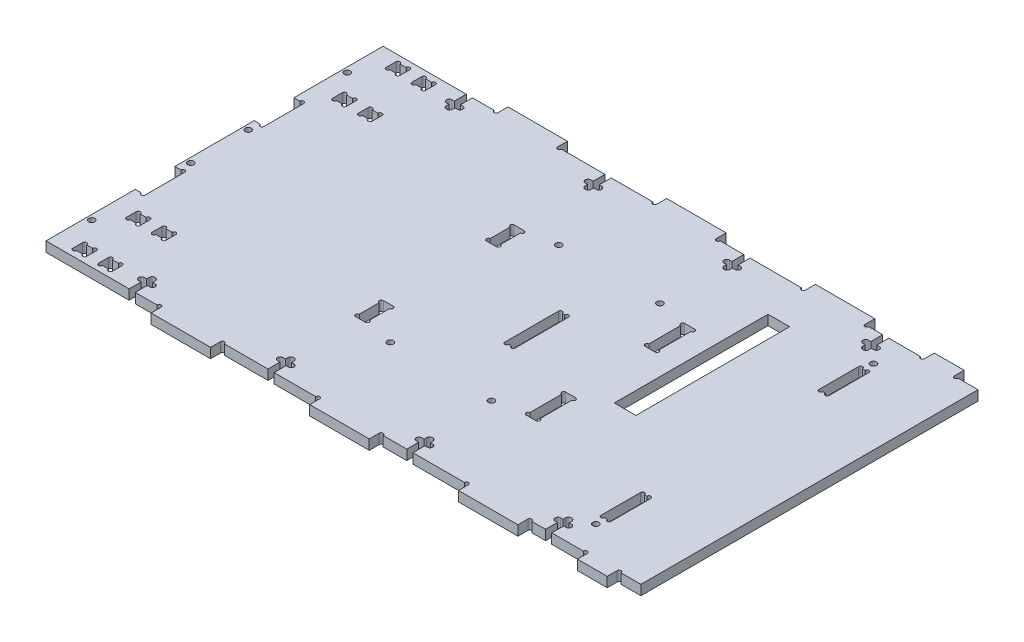
SolidWorks part; units mm, degrees
ref_plane "정면" through (0, 0, 0) normal (0, 0, 1) x (1, 0, 0)
ref_plane "윗면" through (0, 0, 0) normal (0, 1, 0) x (1, 0, 0)
ref_plane "우측면" through (0, 0, 0) normal (1, 0, 0) x (0, 0, -1)
sketch "스케치1" plane through (0, 0, 0) normal (0, 1, 0) x (1, 0, 0)
  line L1 (0, 0) -> (300, 0)
  line L2 (0, 0) -> (0, 170)
  line L3 (0, 170) -> (300, 170)
  line L4 (300, 0) -> (300, 170)
  dimension "D1" = 170
  dimension "D2" = 300
extrude "보스-돌출1" add sketch "스케치1" along normal blind 5
sketch "스케치2" plane through (0, 0, 0) normal (0, -1, 0) x (1, 0, 0)
  line L0 (159.9, -71.5) -> (159.9, 0) construction
  line L1 (159.9, -71.5) -> (165.1, -71.5)
  line L2 (159.9, -71.5) -> (159.9, -98.5)
  line L3 (159.9, -98.5) -> (165.1, -98.5)
  line L4 (165.1, -71.5) -> (165.1, -98.5)
  line L5 (0, 0) -> (300, 0) construction
  line L6 (159.9, -98.5) -> (159.9, -170) construction
  line L7 (300, -170) -> (0, -170) construction
  line L10 (300, 0) -> (300, -170) construction
  line L11 (259.8, 0) -> (259.8, -20) construction
  line L12 (259.8, -20) -> (265, -20)
  line L13 (259.8, -20) -> (259.8, -40)
  line L14 (259.8, -40) -> (265, -40)
  line L15 (265, -20) -> (265, -40)
  line L16 (259.8, -130) -> (265, -130)
  line L17 (259.8, -130) -> (259.8, -150)
  line L18 (259.8, -150) -> (265, -150)
  line L19 (265, -130) -> (265, -150)
  line L20 (259.8, -40) -> (259.8, -130) construction
  line L21 (259.8, -150) -> (259.8, -170) construction
  line L22 (265, -130) -> (265, -40) construction
  dimension "D1" = 27
  dimension "D2" = 140.1
  dimension "D3" = 5.2
  dimension "D4" = 20
  dimension "D5" = 20
  dimension "D6" = 40.2
  dimension "D7" = 5.2
extrude "컷-돌출1" cut sketch "스케치2" against normal blind 10
sketch "스케치3" plane through (0, 5, 0) normal (0, 1, 0) x (1, 0, 0)
  line L0 (183.65, 42.5) -> (180.55, 42.5) construction
  line L1 (183.65, 40) -> (183.65, 45) construction
  line L2 (180.55, 40) -> (180.55, 45) construction
  line L3 (180.55, 42.5) -> (132.65, 42.5) construction
  line L4 (132.65, 40) -> (132.65, 45) construction
  line L5 (132.65, 42.5) -> (129.55, 42.5) construction
  line L6 (129.55, 40) -> (129.55, 45) construction
  line L7 (183.65, 127.5) -> (180.55, 127.5) construction
  line L8 (183.65, 125) -> (183.65, 130) construction
  line L9 (180.55, 125) -> (180.55, 130) construction
  line L10 (180.55, 127.5) -> (132.65, 127.5) construction
  line L11 (132.65, 125) -> (132.65, 130) construction
  line L12 (132.65, 127.5) -> (129.55, 127.5) construction
  line L13 (129.55, 125) -> (129.55, 130) construction
  line L15 (2.5, 101) -> (2.5, 97.9) construction
  line L17 (5, 101) -> (0, 101) construction
  line L18 (262.3, 16.55) -> (262.3, 13.45) construction
  line L19 (264.8, 16.55) -> (259.8, 16.55) construction
  line L20 (264.8, 13.45) -> (259.8, 13.45) construction
  line L25 (262.3, 156.55) -> (262.3, 153.45) construction
  line L26 (264.8, 156.55) -> (259.8, 156.55) construction
  line L27 (264.8, 153.45) -> (259.8, 153.45) construction
  line L28 (5, 97.9) -> (0, 97.9) construction
  line L31 (2.5, 151) -> (2.5, 147.9) construction
  line L34 (2.5, 22.1) -> (2.5, 19) construction
  line L35 (5, 22.1) -> (0, 22.1) construction
  line L36 (5, 19) -> (0, 19) construction
  line L37 (2.5, 72.1) -> (2.5, 69) construction
  line L38 (5, 72.1) -> (0, 72.1) construction
  line L39 (5, 69) -> (0, 69) construction
  line L40 (5, 151) -> (0, 151) construction
  line L41 (5, 147.9) -> (0, 147.9) construction
  circle A0 centre (131.1, 127.5) radius 1.55
  circle A1 centre (182.1, 127.5) radius 1.55
  circle A2 centre (182.1, 42.5) radius 1.55
  circle A3 centre (131.1, 42.5) radius 1.55
  circle A4 centre (2.5, 70.55) radius 1.55
  circle A5 centre (2.5, 20.55) radius 1.55
  circle A6 centre (2.5, 99.45) radius 1.55
  circle A7 centre (2.5, 149.45) radius 1.55
  circle A8 centre (262.3, 155) radius 1.55
  circle A10 centre (262.3, 15) radius 1.55
  dimension "D1" = 3.1
extrude "컷-돌출2" cut sketch "스케치3" against normal blind 10
sketch "스케치4" plane through (0, 0, 0) normal (0, -1, 0) x (1, 0, 0)
  line L1 (0, -125) -> (5, -125)
  line L2 (0, -125) -> (0, -105)
  line L3 (0, -105) -> (5, -105)
  line L4 (5, -125) -> (5, -105)
  line L5 (0, -65) -> (5, -65)
  line L6 (0, -65) -> (0, -45)
  line L7 (0, -45) -> (5, -45)
  line L8 (5, -65) -> (5, -45)
extrude "컷-돌출3" cut sketch "스케치4" against normal blind 5
sketch "스케치5" plane through (0, 0, 0) normal (0, -1, 0) x (1, 0, 0)
  line L2 (5, -45) -> (0, -45) construction
  line L3 (0, -65) -> (5, -65) construction
  line L4 (5, -105) -> (0, -105) construction
  line L5 (0, -125) -> (5, -125) construction
  line L6 (159.9, -98.5) -> (165.1, -98.5) construction
  line L7 (165.1, -71.5) -> (159.9, -71.5) construction
  line L8 (265, -20) -> (259.8, -20) construction
  line L9 (259.8, -40) -> (265, -40) construction
  line L10 (265, -130) -> (259.8, -130) construction
  line L11 (259.8, -150) -> (265, -150) construction
  circle A1 centre (4, -45) radius 1
  circle A2 centre (4, -65) radius 1
  circle A5 centre (4, -105) radius 1
  circle A6 centre (4, -125) radius 1
  circle A8 centre (164.1, -98.5) radius 1
  circle A9 centre (160.9, -98.5) radius 1
  circle A10 centre (164.1, -71.5) radius 1
  circle A11 centre (160.9, -71.5) radius 1
  circle A12 centre (264, -20) radius 1
  circle A13 centre (260.8, -20) radius 1
  circle A14 centre (264, -40) radius 1
  circle A15 centre (260.8, -40) radius 1
  circle A16 centre (264, -130) radius 1
  circle A17 centre (260.8, -130) radius 1
  circle A18 centre (264, -150) radius 1
  circle A19 centre (260.8, -150) radius 1
  dimension "D1" = 2
extrude "컷-돌출4" cut sketch "스케치5" against normal blind 10
sketch "스케치8" plane through (0, 0, 0) normal (0, -1, 0) x (1, 0, 0)
  line L0 (0, 0) -> (300, 0) construction
  line L1 (58, 0) -> (88, 0)
  line L2 (58, 0) -> (58, 5)
  line L3 (58, 5) -> (88, 5)
  line L4 (88, 0) -> (88, 5)
  line L5 (0, 5) -> (58, 5) construction
  line L6 (0, 0) -> (300, 0) construction
  line L7 (138, 5) -> (168, 5)
  line L8 (138, 5) -> (138, 0)
  line L9 (138, 0) -> (168, 0)
  line L10 (168, 5) -> (168, 0)
  line L11 (0, 0) -> (300, 0) construction
  line L12 (213, 5) -> (243, 5)
  line L13 (213, 5) -> (213, 0)
  line L14 (213, 0) -> (243, 0)
  line L15 (243, 5) -> (243, 0)
  line L16 (0, 0) -> (300, 0) construction
  line L17 (273, 5) -> (288, 5)
  line L18 (273, 5) -> (273, 0)
  line L19 (273, 0) -> (288, 0)
  line L20 (288, 5) -> (288, 0)
  line L21 (300, 0) -> (300, -170) construction
  line L22 (0, -85) -> (300, -85) construction
  line L23 (0, -105) -> (0, -65) construction
  line L24 (288, -175) -> (288, -170)
  line L25 (273, -170) -> (288, -170)
  line L26 (273, -175) -> (273, -170)
  line L27 (273, -175) -> (288, -175)
  line L28 (243, -175) -> (243, -170)
  line L29 (213, -170) -> (243, -170)
  line L30 (213, -175) -> (213, -170)
  line L31 (213, -175) -> (243, -175)
  line L32 (168, -175) -> (168, -170)
  line L33 (138, -170) -> (168, -170)
  line L34 (138, -175) -> (138, -170)
  line L35 (138, -175) -> (168, -175)
  line L36 (88, -170) -> (88, -175)
  line L37 (58, -175) -> (88, -175)
  line L38 (58, -170) -> (58, -175)
  line L39 (58, -170) -> (88, -170)
  dimension "D1" = 12
  dimension "D2" = 15
  dimension "D3" = 30
  dimension "D4" = 30
  dimension "D5" = 45
  dimension "D6" = 30
  dimension "D7" = 50
  dimension "D8" = 30
extrude "보스-돌출2" add sketch "스케치8" against normal blind 5
sketch "스케치9" plane through (0, 0, 0) normal (0, -1, 0) x (1, 0, 0)
  line L0 (0, 0) -> (58, 0) construction
  line L1 (88, 0) -> (138, 0) construction
  line L2 (88, 0) -> (138, 0) construction
  line L3 (168, 0) -> (213, 0) construction
  line L4 (168, 0) -> (213, 0) construction
  line L5 (243, 0) -> (273, 0) construction
  line L6 (243, 0) -> (273, 0) construction
  line L7 (288, 0) -> (300, 0) construction
  line L8 (0, -85) -> (300, -85) construction
  line L9 (0, -105) -> (0, -65) construction
  line L10 (300, 0) -> (300, -170) construction
  circle A0 centre (57, 0) radius 1
  circle A1 centre (89, 0) radius 1
  circle A2 centre (137, 0) radius 1
  circle A3 centre (169, 0) radius 1
  circle A4 centre (212, 0) radius 1
  circle A5 centre (272, 0) radius 1
  circle A6 centre (244, 0) radius 1
  circle A7 centre (289, 0) radius 1
  circle A8 centre (289, -170) radius 1
  circle A9 centre (244, -170) radius 1
  circle A10 centre (272, -170) radius 1
  circle A11 centre (212, -170) radius 1
  circle A12 centre (169, -170) radius 1
  circle A13 centre (137, -170) radius 1
  circle A14 centre (89, -170) radius 1
  circle A15 centre (57, -170) radius 1
  dimension "D1" = 2
extrude "컷-돌출6" cut sketch "스케치9" against normal blind 5
sketch "스케치13" plane through (0, 5, 0) normal (0, 1, 0) x (1, 0, 0)
  line L0 (30, 8.5) -> (30, 30.5) construction
  line L1 (30, 8.5) -> (23, 8.5)
  line L2 (30, 8.5) -> (30, 3.5)
  line L3 (30, 3.5) -> (23, 3.5)
  line L4 (23, 8.5) -> (23, 3.5)
  line L5 (17, 8.5) -> (10, 8.5)
  line L6 (17, 8.5) -> (17, 3.5)
  line L7 (17, 3.5) -> (10, 3.5)
  line L8 (10, 8.5) -> (10, 3.5)
  line L9 (30, 19.5) -> (11.9274, 19.5) construction
  line L10 (10, 30.5) -> (10, 35.5)
  line L11 (17, 35.5) -> (10, 35.5)
  line L12 (17, 30.5) -> (17, 35.5)
  line L13 (17, 30.5) -> (10, 30.5)
  line L14 (23, 30.5) -> (23, 35.5)
  line L15 (30, 35.5) -> (23, 35.5)
  line L16 (30, 30.5) -> (30, 35.5)
  line L17 (30, 30.5) -> (23, 30.5)
  line L18 (0, 85) -> (49.672, 85) construction
  line L19 (0, 105) -> (0, 65) construction
  line L20 (30, 150.5) -> (11.9274, 150.5) construction
  line L21 (30, 161.5) -> (30, 139.5) construction
  line L22 (30, 139.5) -> (23, 139.5)
  line L23 (30, 139.5) -> (30, 134.5)
  line L24 (30, 134.5) -> (23, 134.5)
  line L25 (23, 139.5) -> (23, 134.5)
  line L26 (17, 139.5) -> (10, 139.5)
  line L27 (17, 139.5) -> (17, 134.5)
  line L28 (17, 134.5) -> (10, 134.5)
  line L29 (10, 139.5) -> (10, 134.5)
  line L30 (10, 161.5) -> (10, 166.5)
  line L31 (17, 166.5) -> (10, 166.5)
  line L32 (17, 161.5) -> (17, 166.5)
  line L33 (17, 161.5) -> (10, 161.5)
  line L34 (23, 161.5) -> (23, 166.5)
  line L35 (30, 166.5) -> (23, 166.5)
  line L36 (30, 161.5) -> (30, 166.5)
  line L37 (30, 161.5) -> (23, 161.5)
extrude "컷-돌출9" cut sketch "스케치13" against normal blind 10
sketch "스케치14" plane through (0, 0, 0) normal (0, -1, 0) x (1, 0, 0)
  line L0 (10, -8.5) -> (17, -8.5) construction
  line L1 (17, -3.5) -> (10, -3.5) construction
  line L2 (17, -30.5) -> (23, -30.5) construction
  line L3 (23, -30.5) -> (23, -8.5) construction
  line L4 (23, -8.5) -> (17, -8.5) construction
  line L5 (17, -8.5) -> (17, -30.5) construction
  line L6 (20, -30.5) -> (20, -8.5) construction
  line L7 (17, -19.5) -> (23, -19.5) construction
  line L8 (0, -85) -> (55.1733, -85) construction
  line L9 (0, -105) -> (0, -65) construction
  line L10 (17, -150.5) -> (23, -150.5) construction
  line L11 (20, -139.5) -> (20, -161.5) construction
  line L12 (17, -161.5) -> (17, -139.5) construction
  line L13 (23, -161.5) -> (17, -161.5) construction
  line L14 (23, -139.5) -> (23, -161.5) construction
  line L15 (17, -139.5) -> (23, -139.5) construction
  circle A0 centre (11, -8.5) radius 1
  circle A1 centre (11, -3.5) radius 1
  circle A2 centre (16, -3.5) radius 1
  circle A3 centre (16, -8.5) radius 1
  circle A4 centre (24, -8.5) radius 1
  circle A5 centre (24, -3.5) radius 1
  circle A6 centre (29, -3.5) radius 1
  circle A7 centre (29, -8.5) radius 1
  circle A8 centre (29, -30.5) radius 1
  circle A9 centre (29, -35.5) radius 1
  circle A10 centre (24, -35.5) radius 1
  circle A11 centre (24, -30.5) radius 1
  circle A12 centre (16, -30.5) radius 1
  circle A13 centre (16, -35.5) radius 1
  circle A14 centre (11, -35.5) radius 1
  circle A15 centre (11, -30.5) radius 1
  circle A16 centre (11, -139.5) radius 1
  circle A17 centre (11, -134.5) radius 1
  circle A18 centre (16, -134.5) radius 1
  circle A19 centre (16, -139.5) radius 1
  circle A20 centre (24, -139.5) radius 1
  circle A21 centre (24, -134.5) radius 1
  circle A22 centre (29, -134.5) radius 1
  circle A23 centre (29, -139.5) radius 1
  circle A24 centre (29, -161.5) radius 1
  circle A25 centre (29, -166.5) radius 1
  circle A26 centre (24, -166.5) radius 1
  circle A27 centre (24, -161.5) radius 1
  circle A28 centre (16, -161.5) radius 1
  circle A29 centre (16, -166.5) radius 1
  circle A30 centre (11, -166.5) radius 1
  circle A31 centre (11, -161.5) radius 1
  dimension "D1" = 2
extrude "컷-돌출10" cut sketch "스케치14" against normal blind 10
sketch "스케치15" plane through (0, 5, 0) normal (0, 1, 0) x (1, 0, 0)
  line L1 (111.1, 125) -> (116.1, 125)
  line L2 (111.1, 125) -> (111.1, 111)
  line L3 (111.1, 111) -> (116.1, 111)
  line L4 (116.1, 125) -> (116.1, 111)
  line L5 (111.1, 45) -> (116.1, 45)
  line L6 (111.1, 45) -> (111.1, 59)
  line L7 (111.1, 59) -> (116.1, 59)
  line L8 (116.1, 45) -> (116.1, 59)
  line L9 (197.1, 65) -> (202.1, 65)
  line L10 (197.1, 65) -> (197.1, 45)
  line L11 (197.1, 45) -> (202.1, 45)
  line L12 (202.1, 65) -> (202.1, 45)
  line L13 (197.1, 105) -> (202.1, 105)
  line L14 (197.1, 105) -> (197.1, 125)
  line L15 (197.1, 125) -> (202.1, 125)
  line L16 (202.1, 105) -> (202.1, 125)
  arc A0 (116.1, 56.5) -> (116.1, 59) centre (116.1, 57.75) ccw construction
  dimension "D1" = 5
extrude "컷-돌출11" cut sketch "스케치15" against normal blind 10
sketch "스케치16" plane through (0, 5, 0) normal (0, 1, 0) x (1, 0, 0)
  line L0 (111.1, 59) -> (111.1, 45) construction
  line L1 (116.1, 45) -> (116.1, 59) construction
  line L2 (111.1, 125) -> (111.1, 111) construction
  line L3 (116.1, 111) -> (116.1, 125) construction
  line L4 (202.1, 105) -> (202.1, 125) construction
  line L5 (197.1, 125) -> (197.1, 105) construction
  line L6 (197.1, 65) -> (197.1, 45) construction
  line L7 (202.1, 45) -> (202.1, 65) construction
  circle A0 centre (111.1, 46) radius 1
  circle A1 centre (116.1, 46) radius 1
  circle A2 centre (116.1, 58) radius 1
  circle A3 centre (111.1, 58) radius 1
  circle A4 centre (111.1, 112) radius 1
  circle A5 centre (116.1, 112) radius 1
  circle A6 centre (116.1, 124) radius 1
  circle A7 centre (111.1, 124) radius 1
  circle A8 centre (202.1, 124) radius 1
  circle A10 centre (197.1, 124) radius 1
  circle A11 centre (197.1, 64) radius 1
  circle A12 centre (202.1, 64) radius 1
  circle A13 centre (202.1, 106) radius 1
  circle A14 centre (197.1, 106) radius 1
  circle A15 centre (197.1, 46) radius 1
  circle A16 centre (202.1, 46) radius 1
  dimension "D1" = 2
extrude "컷-돌출12" cut sketch "스케치16" against normal blind 10
sketch "스케치17" plane through (0, 5, 0) normal (0, 1, 0) x (1, 0, 0)
  line L0 (219.1, 97.5569) -> (219.1, 95.1974) construction
  line L1 (214.1, 72.5) -> (225, 72.5)
  line L2 (214.1, 72.5) -> (214.1, 150)
  line L3 (214.1, 150) -> (225, 150)
  line L4 (225, 72.5) -> (225, 150)
  line L6 (220, 97.5569) -> (220, 95.1974) construction
  line L7 (2.5, -7.5) -> (297.5, -7.5) construction
  line L8 (211, 170) -> (170, 170) construction
  dimension "D1" = 5
  dimension "D2" = 5
  dimension "D3" = 80
  dimension "D4" = 20
extrude "컷-돌출13" cut sketch "스케치17" against normal blind 10
sketch "스케치7" plane through (0, 0, 0) normal (0, -1, 0) x (1, 0, 0)
  line L0 (115.0287, -170) -> (111.9287, -170)
  line L1 (115.0287, -164) -> (116.2287, -164)
  line L2 (115.0287, -161.2) -> (115.0287, -160)
  line L3 (111.9287, -161.2) -> (111.9287, -160)
  line L4 (111.9287, -161.2) -> (110.7287, -161.2)
  line L5 (111.9287, -170) -> (111.9287, -164)
  line L6 (110.7287, -164) -> (111.9287, -164)
  line L7 (115.0287, -170) -> (115.0287, -164)
  line L8 (116.2287, -161.2) -> (115.0287, -161.2)
  line L9 (115.0287, -161.2) -> (111.9287, -161.2) construction
  line L10 (115.0287, -161.2) -> (115.0287, -164) construction
  line L11 (111.9287, -164) -> (111.9287, -161.2) construction
  line L12 (115.0287, -160) -> (111.9287, -160) construction
  line L13 (113.4787, -160) -> (113.4787, -157.529) construction
  line L14 (110.7287, -161.2) -> (110.7287, -164) construction
  line L15 (116.2287, -164) -> (116.2287, -161.2) construction
  line L16 (115.0287, -164) -> (111.9287, -164) construction
  line L17 (185.0287, -170) -> (181.9287, -170)
  line L18 (185.0287, -164) -> (186.2287, -164)
  line L19 (185.0287, -161.2) -> (185.0287, -160)
  line L20 (181.9287, -161.2) -> (181.9287, -160)
  line L21 (181.9287, -161.2) -> (180.7287, -161.2)
  line L22 (181.9287, -170) -> (181.9287, -164)
  line L23 (180.7287, -164) -> (181.9287, -164)
  line L24 (185.0287, -170) -> (185.0287, -164)
  line L25 (186.2287, -161.2) -> (185.0287, -161.2)
  line L26 (185.0287, -161.2) -> (181.9287, -161.2) construction
  line L27 (185.0287, -161.2) -> (185.0287, -164) construction
  line L28 (181.9287, -164) -> (181.9287, -161.2) construction
  line L29 (185.0287, -160) -> (181.9287, -160) construction
  line L30 (45.0287, -161.2) -> (41.9287, -161.2) construction
  line L31 (45.0287, -161.2) -> (45.0287, -164) construction
  line L32 (41.9287, -164) -> (41.9287, -161.2) construction
  line L33 (45.0287, -160) -> (41.9287, -160) construction
  line L34 (43.4787, -160) -> (43.4787, -157.529) construction
  line L35 (183.4787, -160) -> (183.4787, -157.529) construction
  line L36 (180.7287, -161.2) -> (180.7287, -164) construction
  line L37 (186.2287, -164) -> (186.2287, -161.2) construction
  line L38 (185.0287, -164) -> (181.9287, -164) construction
  line L39 (255.0287, -170) -> (251.9287, -170)
  line L40 (255.0287, -164) -> (256.2287, -164)
  line L41 (255.0287, -161.2) -> (255.0287, -160)
  line L42 (251.9287, -161.2) -> (251.9287, -160)
  line L43 (251.9287, -161.2) -> (250.7287, -161.2)
  line L44 (251.9287, -170) -> (251.9287, -164)
  line L45 (250.7287, -164) -> (251.9287, -164)
  line L46 (255.0287, -170) -> (255.0287, -164)
  line L47 (256.2287, -161.2) -> (255.0287, -161.2)
  line L48 (255.0287, -161.2) -> (251.9287, -161.2) construction
  line L49 (255.0287, -161.2) -> (255.0287, -164) construction
  line L50 (251.9287, -164) -> (251.9287, -161.2) construction
  line L51 (255.0287, -160) -> (251.9287, -160) construction
  line L52 (253.4787, -160) -> (253.4787, -157.529) construction
  line L53 (250.7287, -161.2) -> (250.7287, -164) construction
  line L54 (256.2287, -164) -> (256.2287, -161.2) construction
  line L55 (255.0287, -164) -> (251.9287, -164) construction
  line L56 (45.0287, -6) -> (41.9287, -6) construction
  line L57 (46.2287, -6) -> (46.2287, -8.8) construction
  line L58 (40.7287, -8.8) -> (40.7287, -6) construction
  line L59 (255.0287, -6) -> (251.9287, -6) construction
  line L60 (256.2287, -6) -> (256.2287, -8.8) construction
  line L61 (250.7287, -8.8) -> (250.7287, -6) construction
  line L62 (253.4787, -10) -> (253.4787, -12.471) construction
  line L63 (255.0287, -10) -> (251.9287, -10) construction
  line L64 (251.9287, -6) -> (251.9287, -8.8) construction
  line L65 (255.0287, -8.8) -> (255.0287, -6) construction
  line L66 (255.0287, -8.8) -> (251.9287, -8.8) construction
  line L67 (185.0287, -6) -> (181.9287, -6) construction
  line L68 (186.2287, -6) -> (186.2287, -8.8) construction
  line L69 (40.7287, -161.2) -> (40.7287, -164) construction
  line L71 (180.7287, -8.8) -> (180.7287, -6) construction
  line L72 (183.4787, -10) -> (183.4787, -12.471) construction
  line L73 (43.4787, -10) -> (43.4787, -12.471) construction
  line L74 (45.0287, -10) -> (41.9287, -10) construction
  line L75 (0, -85) -> (300, -85) construction
  line L76 (0, -105) -> (0, -65) construction
  line L77 (300, 0) -> (300, -170) construction
  line L78 (46.2287, -164) -> (46.2287, -161.2) construction
  line L79 (45.0287, -164) -> (41.9287, -164) construction
  line L80 (41.9287, -6) -> (41.9287, -8.8) construction
  line L81 (45.0287, -8.8) -> (45.0287, -6) construction
  line L82 (45.0287, -8.8) -> (41.9287, -8.8) construction
  line L83 (185.0287, -10) -> (181.9287, -10) construction
  line L84 (181.9287, -6) -> (181.9287, -8.8) construction
  line L85 (185.0287, -8.8) -> (185.0287, -6) construction
  line L86 (185.0287, -8.8) -> (181.9287, -8.8) construction
  line L87 (115.0287, -6) -> (111.9287, -6) construction
  line L88 (116.2287, -6) -> (116.2287, -8.8) construction
  line L89 (110.7287, -8.8) -> (110.7287, -6) construction
  line L90 (113.4787, -10) -> (113.4787, -12.471) construction
  line L91 (115.0287, -10) -> (111.9287, -10) construction
  line L92 (111.9287, -6) -> (111.9287, -8.8) construction
  line L93 (115.0287, -8.8) -> (115.0287, -6) construction
  line L94 (115.0287, -8.8) -> (111.9287, -8.8) construction
  line L95 (46.2287, -8.8) -> (45.0287, -8.8)
  line L96 (45.0287, 0) -> (45.0287, -6)
  line L97 (45.0287, -170) -> (41.9287, -170)
  line L98 (45.0287, -164) -> (46.2287, -164)
  line L99 (45.0287, -161.2) -> (45.0287, -160)
  line L100 (41.9287, -161.2) -> (41.9287, -160)
  line L101 (41.9287, -161.2) -> (40.7287, -161.2)
  line L102 (41.9287, -170) -> (41.9287, -164)
  line L103 (40.7287, -164) -> (41.9287, -164)
  line L104 (45.0287, -170) -> (45.0287, -164)
  line L105 (46.2287, -161.2) -> (45.0287, -161.2)
  line L106 (325.0287, -170) -> (321.9287, -170) [skipped]
  line L107 (325.0287, -164) -> (326.2287, -164) [skipped]
  line L108 (325.0287, -161.2) -> (325.0287, -160) [skipped]
  line L109 (321.9287, -161.2) -> (321.9287, -160) [skipped]
  line L110 (321.9287, -161.2) -> (320.7287, -161.2) [skipped]
  line L111 (321.9287, -170) -> (321.9287, -164) [skipped]
  line L112 (320.7287, -164) -> (321.9287, -164) [skipped]
  line L113 (325.0287, -170) -> (325.0287, -164) [skipped]
  line L114 (326.2287, -161.2) -> (325.0287, -161.2) [skipped]
  line L115 (325.0287, -161.2) -> (321.9287, -161.2) construction
  line L116 (325.0287, -161.2) -> (325.0287, -164) construction
  line L117 (321.9287, -164) -> (321.9287, -161.2) construction
  line L118 (325.0287, -160) -> (321.9287, -160) construction
  line L119 (323.4787, -160) -> (323.4787, -157.529) construction
  line L120 (320.7287, -161.2) -> (320.7287, -164) construction
  line L121 (326.2287, -164) -> (326.2287, -161.2) construction
  line L122 (325.0287, -164) -> (321.9287, -164) construction
  line L123 (40.7287, -6) -> (41.9287, -6)
  line L124 (41.9287, 0) -> (41.9287, -6)
  line L125 (41.9287, -8.8) -> (40.7287, -8.8)
  line L126 (41.9287, -8.8) -> (41.9287, -10)
  line L127 (45.0287, -8.8) -> (45.0287, -10)
  line L128 (45.0287, -6) -> (46.2287, -6)
  line L129 (45.0287, 0) -> (41.9287, 0)
  line L130 (256.2287, -8.8) -> (255.0287, -8.8)
  line L131 (255.0287, 0) -> (255.0287, -6)
  line L132 (250.7287, -6) -> (251.9287, -6)
  line L133 (251.9287, 0) -> (251.9287, -6)
  line L134 (251.9287, -8.8) -> (250.7287, -8.8)
  line L135 (251.9287, -8.8) -> (251.9287, -10)
  line L136 (255.0287, -8.8) -> (255.0287, -10)
  line L137 (255.0287, -6) -> (256.2287, -6)
  line L138 (255.0287, 0) -> (251.9287, 0)
  line L139 (186.2287, -8.8) -> (185.0287, -8.8)
  line L140 (185.0287, 0) -> (185.0287, -6)
  line L141 (180.7287, -6) -> (181.9287, -6)
  line L142 (181.9287, 0) -> (181.9287, -6)
  line L143 (181.9287, -8.8) -> (180.7287, -8.8)
  line L144 (181.9287, -8.8) -> (181.9287, -10)
  line L145 (185.0287, -8.8) -> (185.0287, -10)
  line L146 (185.0287, -6) -> (186.2287, -6)
  line L147 (185.0287, 0) -> (181.9287, 0)
  line L148 (116.2287, -8.8) -> (115.0287, -8.8)
  line L149 (115.0287, 0) -> (115.0287, -6)
  line L150 (110.7287, -6) -> (111.9287, -6)
  line L151 (111.9287, 0) -> (111.9287, -6)
  line L152 (111.9287, -8.8) -> (110.7287, -8.8)
  line L153 (111.9287, -8.8) -> (111.9287, -10)
  line L154 (115.0287, -8.8) -> (115.0287, -10)
  line L155 (115.0287, -6) -> (116.2287, -6)
  line L156 (115.0287, 0) -> (111.9287, 0)
  arc A0 (111.9287, -160) -> (115.0287, -160) centre (113.4787, -160) cw
  arc A1 (116.2287, -161.2) -> (116.2287, -164) centre (116.2287, -162.6) cw
  arc A2 (110.7287, -164) -> (110.7287, -161.2) centre (110.7287, -162.6) cw
  arc A3 (181.9287, -160) -> (185.0287, -160) centre (183.4787, -160) cw
  arc A4 (186.2287, -161.2) -> (186.2287, -164) centre (186.2287, -162.6) cw
  arc A5 (180.7287, -164) -> (180.7287, -161.2) centre (180.7287, -162.6) cw
  arc A6 (251.9287, -160) -> (255.0287, -160) centre (253.4787, -160) cw
  arc A7 (256.2287, -161.2) -> (256.2287, -164) centre (256.2287, -162.6) cw
  arc A8 (250.7287, -164) -> (250.7287, -161.2) centre (250.7287, -162.6) cw
  arc A9 (40.7287, -6) -> (40.7287, -8.8) centre (40.7287, -7.4) ccw
  arc A10 (46.2287, -8.8) -> (46.2287, -6) centre (46.2287, -7.4) ccw
  arc A11 (41.9287, -10) -> (45.0287, -10) centre (43.4787, -10) ccw
  arc A12 (250.7287, -6) -> (250.7287, -8.8) centre (250.7287, -7.4) ccw
  arc A13 (41.9287, -160) -> (45.0287, -160) centre (43.4787, -160) cw
  arc A14 (46.2287, -161.2) -> (46.2287, -164) centre (46.2287, -162.6) cw
  arc A15 (40.7287, -164) -> (40.7287, -161.2) centre (40.7287, -162.6) cw
  arc A16 (321.9287, -160) -> (325.0287, -160) centre (323.4787, -160) cw [skipped]
  arc A17 (326.2287, -161.2) -> (326.2287, -164) centre (326.2287, -162.6) cw [skipped]
  arc A18 (320.7287, -164) -> (320.7287, -161.2) centre (320.7287, -162.6) cw [skipped]
  arc A19 (256.2287, -8.8) -> (256.2287, -6) centre (256.2287, -7.4) ccw
  arc A20 (251.9287, -10) -> (255.0287, -10) centre (253.4787, -10) ccw
  arc A21 (180.7287, -6) -> (180.7287, -8.8) centre (180.7287, -7.4) ccw
  arc A22 (186.2287, -8.8) -> (186.2287, -6) centre (186.2287, -7.4) ccw
  arc A23 (181.9287, -10) -> (185.0287, -10) centre (183.4787, -10) ccw
  arc A24 (110.7287, -6) -> (110.7287, -8.8) centre (110.7287, -7.4) ccw
  arc A25 (116.2287, -8.8) -> (116.2287, -6) centre (116.2287, -7.4) ccw
  arc A26 (111.9287, -10) -> (115.0287, -10) centre (113.4787, -10) ccw
  dimension "D1" = 5
extrude "컷-돌출5" cut sketch "스케치7" against normal blind 10
sketch "스케치18" plane through (0, 0, 0) normal (0, -1, 0) x (1, 0, 0)
  line L0 (0, -85) -> (300, -85) construction
  line L1 (0, -105) -> (0, -65) construction
  line L2 (300, 0) -> (300, -170) construction
  line L4 (285, -152.5) -> (15, -152.5) construction
  line L5 (285, -152.5) -> (285, -17.5) construction
  line L6 (285, -17.5) -> (15, -17.5) construction
  line L7 (15, -152.5) -> (15, -17.5) construction
  line L8 (285, -152.5) -> (15, -17.5) construction
  line L9 (285, -17.5) -> (15, -152.5) construction
  circle A0 centre (15, -17.5) radius 6
  circle A1 centre (15, -152.5) radius 6
  circle A2 centre (285, -17.5) radius 6
  circle A3 centre (285, -152.5) radius 6
  point P6 (150, -85)
  dimension "D3" = 12
  dimension "D1" = 135
  dimension "D2" = 270
extrude "컷-돌출14" cut sketch "스케치18" against normal blind 1.5
sketch "스케치19" plane through (0, 5, 0) normal (0, 1, 0) x (1, 0, 0)
  line L0 (111.1, 123) -> (111.1, 113) construction
  line L1 (111, 123.914) -> (116.2, 123.914)
  line L2 (111, 123.914) -> (111, 112.1352)
  line L3 (111, 112.1352) -> (116.2, 112.1352)
  line L4 (116.2, 123.914) -> (116.2, 112.1352)
  line L5 (111, 57.988) -> (116.2, 57.988)
  line L6 (111, 57.988) -> (111, 46.2932)
  line L7 (111, 46.2932) -> (116.2, 46.2932)
  line L8 (116.2, 57.988) -> (116.2, 46.2932)
  line L9 (197, 63.9937) -> (202.2, 63.9937)
  line L10 (197, 63.9937) -> (197, 46.6181)
  line L11 (197, 46.6181) -> (202.2, 46.6181)
  line L12 (202.2, 63.9937) -> (202.2, 46.6181)
  line L13 (197, 123.914) -> (202.2, 123.914)
  line L14 (197, 123.914) -> (197, 106.2522)
  line L15 (197, 106.2522) -> (202.2, 106.2522)
  line L16 (202.2, 123.914) -> (202.2, 106.2522)
  line L17 (116.1, 113) -> (116.1, 123) construction
  line L18 (111.1, 57) -> (111.1, 47) construction
  line L19 (116.1, 47) -> (116.1, 57) construction
  line L20 (197.1, 63) -> (197.1, 47) construction
  line L21 (202.1, 47) -> (202.1, 63) construction
  line L22 (197.1, 123) -> (197.1, 107) construction
  line L23 (202.1, 107) -> (202.1, 123) construction
  dimension "D1" = 0.1
  dimension "D2" = 0.1
  dimension "D3" = 0.1
  dimension "D4" = 0.1
  dimension "D5" = 0.1
  dimension "D6" = 0.1
  dimension "D7" = 0.1
  dimension "D8" = 0.1
extrude "컷-돌출15" cut sketch "스케치19" against normal blind 10
